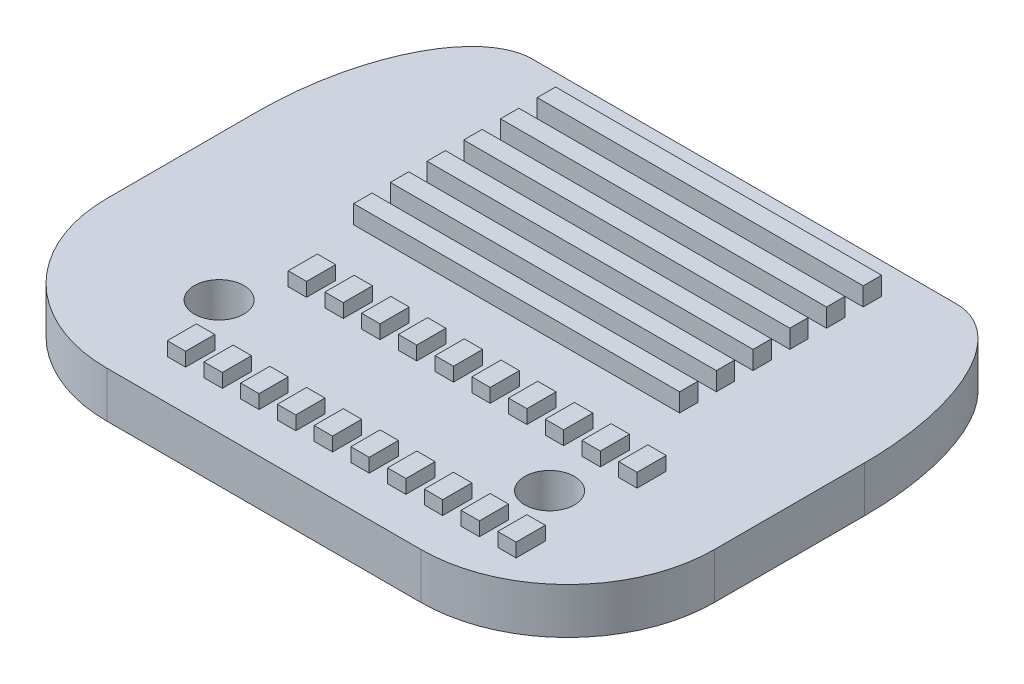
SolidWorks part; units mm, degrees
ref_plane "Front Plane" through (0, 0, 0) normal (0, 0, 1) x (1, 0, 0)
ref_plane "Top Plane" through (0, 0, 0) normal (0, 1, 0) x (1, 0, 0)
ref_plane "Right Plane" through (0, 0, 0) normal (1, 0, 0) x (0, 0, -1)
sketch "Sketch8" plane through (0, 0, 0) normal (0, 1, 0) x (1, 0, 0)
  line L1 (0, 0) -> (33.0989, 0)
  line L2 (0, 0) -> (0, 26.1663)
  line L3 (0, 26.1663) -> (33.0989, 26.1663)
  line L4 (33.0989, 0) -> (33.0989, 26.1663)
  line L5 (16.8356, 0) -> (16.8356, 2.1913) construction
  line L6 (16.8356, 3.7788) -> (16.8356, 6.2788) construction
  line L7 (16.8356, 10.3663) -> (16.8356, 11.8663) construction
  line L9 (16.8356, 6.2788) -> (16.8356, 8.7788) construction
  line L16 (33.0989, 2.1913) -> (6.3356, 2.1913) construction
  line L17 (6.3356, 2.1913) -> (6.3356, 3.7788) construction
  line L18 (6.3356, 3.7788) -> (33.0989, 3.7788) construction
  line L19 (33.0989, 8.7788) -> (6.3356, 8.7788) construction
  line L20 (6.3356, 8.7788) -> (6.3356, 10.3663) construction
  line L21 (6.3356, 10.3663) -> (33.0989, 10.3663) construction
  line L24 (7.8356, 6.2788) -> (25.8356, 6.2788) construction
  point P40 (16.8356, 6.2788)
  point P47 (7.8356, 6.2788)
  point P48 (25.8356, 6.2788)
  dimension "D1" = 26.1663
  dimension "D2" = 33.0989
  dimension "D3" = 1.5875
  dimension "D4" = 18
  dimension "D5" = 6.2788
  dimension "D6" = 2.5
  dimension "D7" = 26.7633
  dimension "D8" = 2.1913
  dimension "D9" = 1.5
  dimension "D10" = 16.2633
extrude "Boss-Extrude5" add sketch "Sketch8" against normal blind 2.5 separate body
hole_wizard "M2.5 Clearance Hole2" positions "Sketch9" profile "Sketch10" hole size "M2.5" standard "ANSI Metric"
sketch "Sketch9" plane through (0, 0, 0) normal (0, 1, 0) x (1, 0, 0)
  point P0 (7.8356, 6.2788)
  point P3 (25.8356, 6.2788)
sketch "Sketch10" plane through (7.8356, 0, -6.2788) normal (1, 0, 0) x (0, 0, 1)
  line L0 (0, 0) -> (0, 12)
  line L1 (0, 12) -> (1.35, 11.1888)
  line L2 (1.35, 11.1888) -> (1.35, 0)
  line L5 (1.35, 0) -> (0, 0)
  line L10 (0, 12) -> (-1.35, 11.1888) construction
  line L11 (0, -6.35) -> (0, 107.95) construction
  dimension "Hole Dia." = 2.7
  dimension "Hole Depth" = 12
  dimension "Drill Angle" = 118
sketch "Sketch11" plane through (0, 0, 0) normal (0, 1, 0) x (1, 0, 0)
  line L0 (6.3356, 10.3663) -> (33.0989, 10.3663) construction
  line L1 (28.0989, 10.3663) -> (27.0989, 10.3663)
  line L2 (28.0989, 10.3663) -> (28.0989, 8.7788)
  line L3 (28.0989, 8.7788) -> (27.0989, 8.7788)
  line L4 (27.0989, 10.3663) -> (27.0989, 8.7788)
  line L5 (33.0989, 8.7788) -> (6.3356, 8.7788) construction
  line L6 (6.3356, 3.7788) -> (33.0989, 3.7788) construction
  line L7 (28.0989, 3.7788) -> (27.0989, 3.7788)
  line L8 (28.0989, 3.7788) -> (28.0989, 2.1913)
  line L9 (28.0989, 2.1913) -> (27.0989, 2.1913)
  line L10 (27.0989, 3.7788) -> (27.0989, 2.1913)
  line L11 (33.0989, 2.1913) -> (6.3356, 2.1913) construction
  line L24 (33.0989, 8.7788) -> (28.0989, 8.7788) construction
  line L25 (27.0989, 8.7788) -> (27.0989, 3.7788) construction
  line L28 (16.8356, 11.8663) -> (16.8356, 13.4814) construction
  line L29 (7.9582, 13.4814) -> (25.713, 13.4814)
  line L30 (7.9582, 13.4814) -> (7.9582, 14.4814)
  line L31 (7.9582, 14.4814) -> (25.713, 14.4814)
  line L32 (25.713, 13.4814) -> (25.713, 14.4814)
  dimension "D1" = 5
  dimension "D2" = 1
  dimension "D3" = 1.6151
  dimension "D4" = 17.7548
extrude "Boss-Extrude6" add sketch "Sketch11" along normal blind 0.75 contours L2 L3 L4 L1 | L8 L9 L10 L7
pattern_linear "LPattern1" count 10 spacing 2 along (-1, 0, 0) of "Boss-Extrude6"
extrude "Boss-Extrude8" add sketch "Sketch11<4>" along normal blind 1 contours L29 L32 L31 L30
sketch "Sketch11<4>" plane through (0, 0, 0) normal (0, 1, 0) x (1, 0, 0) same geometry as "Sketch11"
pattern_linear "LPattern3" count 6 spacing 2 along (0, 0, -1) of "Boss-Extrude8"
fillet "Fillet5" radius 8 2 edges at (33.0989, -1.25, 0) (0, -1.25, 0)
fillet "Fillet8" radius 5 1 edges at (33.0989, -1.25, -26.1663) second distance 10 first distance on face at (16.5494, -1.25, -26.1663)
fillet "Fillet9" radius 10 1 edges at (0, -1.25, -26.1663) second distance 5 first distance on face at (0, -1.25, -17.0831)
